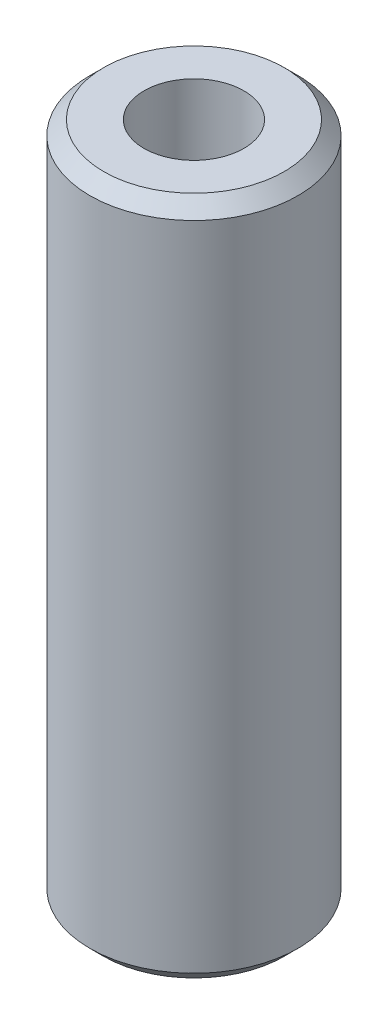
SolidWorks part; units mm, degrees
ref_plane "Front Plane" through (0, 0, 0) normal (0, 0, 1) x (1, 0, 0)
ref_plane "Top Plane" through (0, 0, 0) normal (0, 1, 0) x (1, 0, 0)
ref_plane "Right Plane" through (0, 0, 0) normal (1, 0, 0) x (0, 0, -1)
sketch "Sketch1" plane through (0, 0, 0) normal (0, 1, 0) x (1, 0, 0)
  circle A0 centre (0, 0) radius 45
  dimension "SHAFT_OD" = 90
extrude "Boss-Extrude1" add sketch "Sketch1" along normal blind 293.887
sketch "Sketch2" plane through (0, 0, 0) normal (0, 1, 0) x (1, 0, 0)
  circle A0 centre (0, 0) radius 21.6078
  dimension "BORE_D" = 43.2157
extrude "Cut-Extrude1" cut sketch "Sketch2" along normal through all
chamfer "Chamfer1" distance 5.9909 angle 45 2 edges at (0, 293.887, 45) (0, 0, 45)
